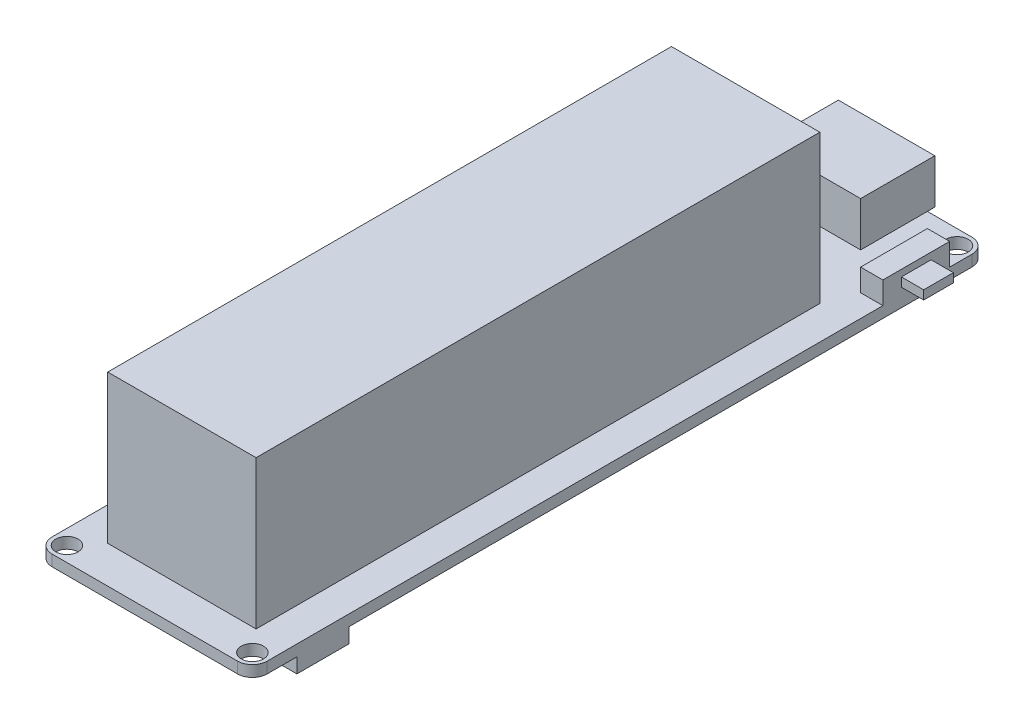
SolidWorks part; units mm, degrees
ref_plane "Front Plane" through (0, 0, 0) normal (0, 0, 1) x (1, 0, 0)
ref_plane "Top Plane" through (0, 0, 0) normal (0, 1, 0) x (1, 0, 0)
ref_plane "Right Plane" through (0, 0, 0) normal (1, 0, 0) x (0, 0, -1)
sketch "Sketch1" plane through (0, 0, 0) normal (0, 1, 0) x (1, 0, 0)
  line L1 (12.5, -49.5) -> (-12.5, -49.5)
  line L2 (14.5, -47.5) -> (14.5, 47.5)
  line L3 (12.5, 49.5) -> (-12.5, 49.5)
  line L4 (-14.5, -47.5) -> (-14.5, 47.5)
  line L5 (14.5, -49.5) -> (-14.5, 49.5) construction
  line L6 (14.5, 49.5) -> (-14.5, -49.5) construction
  arc A0 (14.5, 47.5) -> (12.5, 49.5) centre (12.5, 47.5) ccw
  arc A1 (14.5, -47.5) -> (12.5, -49.5) centre (12.5, -47.5) cw
  arc A2 (-12.5, -49.5) -> (-14.5, -47.5) centre (-12.5, -47.5) cw
  arc A3 (-14.5, 47.5) -> (-12.5, 49.5) centre (-12.5, 47.5) cw
  circle A4 centre (-12.5, 47.5) radius 1.5
  circle A5 centre (12.5, 47.5) radius 1.5
  circle A6 centre (-12.5, -47.5) radius 1.5
  circle A7 centre (12.5, -47.5) radius 1.5
  point P0 (0, 0)
  dimension "D3" = 2
  dimension "D4" = 2
  dimension "D5" = 2
  dimension "D6" = 2
  dimension "D7" = 3
  dimension "D8" = 3
  dimension "D9" = 3
  dimension "D10" = 3
  dimension "D1" = 29
  dimension "D2" = 99
extrude "Boss-Extrude1" add sketch "Sketch1" along normal blind 1.5
sketch "Sketch2" plane through (0, 1.5, 0) normal (0, 1, 0) x (1, 0, 0)
  line L0 (-12.5, -49.5) -> (12.5, -49.5) construction
  line L1 (-10, -44.5) -> (10, -44.5)
  line L2 (-10, -44.5) -> (-10, 31.5)
  line L3 (-10, 31.5) -> (10, 31.5)
  line L4 (10, -44.5) -> (10, 31.5)
  point P6 (0, -49.5)
  point P7 (0, -44.5)
  dimension "D1" = 20
  dimension "D2" = 76
  dimension "D3" = 5
extrude "Boss-Extrude2" add sketch "Sketch2" along normal blind 20
sketch "Sketch3" plane through (0, 1.5, 0) normal (0, 1, 0) x (1, 0, 0)
  line L0 (-14.5, 47.5) -> (-14.5, -47.5) construction
  line L1 (-6.5, 40.5) -> (6.5, 40.5)
  line L2 (-6.5, 40.5) -> (-6.5, 50.5)
  line L3 (-6.5, 50.5) -> (6.5, 50.5)
  line L4 (6.5, 40.5) -> (6.5, 50.5)
  line L5 (-14.5, 33.5) -> (-9.5, 33.5)
  line L6 (-14.5, 33.5) -> (-14.5, 40.5)
  line L7 (-14.5, 40.5) -> (-9.5, 40.5)
  line L8 (-9.5, 33.5) -> (-9.5, 40.5)
  line L9 (14.5, -47.5) -> (14.5, 47.5) construction
  line L10 (14.5, 44.5) -> (11.5, 44.5)
  line L11 (14.5, 44.5) -> (14.5, 35.5)
  line L12 (14.5, 35.5) -> (11.5, 35.5)
  line L13 (11.5, 44.5) -> (11.5, 35.5)
  line L14 (12.5, 49.5) -> (-12.5, 49.5) construction
  line L15 (10, 31.5) -> (-10, 31.5) construction
  point P20 (0, 49.5)
  point P21 (0, 40.5)
  line M15 (12.5, 49.5) -> (-12.5, 49.5)
  line M17 (-14.5, 47.5) -> (-14.5, -47.5)
  line M21 (14.5, -47.5) -> (14.5, 47.5)
  dimension "D1" = 9
  dimension "D2" = 7
  dimension "D3" = 5
  dimension "D4" = 3
  dimension "D5" = 13
  dimension "D6" = 10
  dimension "D7" = 1
  dimension "D8" = 5
  dimension "D9" = 2
extrude "Boss-Extrude3" add sketch "Sketch3" along normal blind 6 contours L1 L4 L2 M15 | L4 L3 L2 M15 region at (0, 1.5, -45) region at (0, 1.5, -50)
extrude "Boss-Extrude4" add sketch "Sketch3<3>" along normal blind 4 contours L5 L8 L7 M17 region at (-12, 1.5, -37)
sketch "Sketch3<3>" plane through (0, 1.5, 0) normal (0, 1, 0) x (1, 0, 0) same geometry as "Sketch3"
extrude "Boss-Extrude5" add sketch "Sketch3<4>" along normal blind 3 contours L10 L13 L12 M21 region at (13, 1.5, -40)
sketch "Sketch3<4>" plane through (0, 1.5, 0) normal (0, 1, 0) x (1, 0, 0) same geometry as "Sketch3"
sketch "Sketch4" plane through (-14.5, 0, 0) normal (-1, 0, 0) x (0, 0, 1)
  line L0 (-33.5, 5.5) -> (-40.5, 1.5) construction
  line L2 (-38.5, 4.5) -> (-35.5, 4.5)
  line L3 (-38.5, 4.5) -> (-38.5, 2.5)
  line L4 (-38.5, 2.5) -> (-35.5, 2.5)
  line L5 (-35.5, 4.5) -> (-35.5, 2.5)
  line L6 (-38.5, 4.5) -> (-35.5, 2.5) construction
  line L7 (-38.5, 2.5) -> (-35.5, 4.5) construction
  point P4 (-37, 3.5)
  dimension "D1" = 3
  dimension "D2" = 2
extrude "Boss-Extrude6" add sketch "Sketch4" along normal blind 1.2
sketch "Sketch5" plane through (14.5, 0, 0) normal (1, 0, 0) x (0, 0, -1)
  line L0 (35.5, 4.5) -> (44.5, 1.5) construction
  line L2 (38, 2.4) -> (42, 2.4)
  line L3 (38, 2.4) -> (38, 3.6)
  line L4 (38, 3.6) -> (42, 3.6)
  line L5 (42, 2.4) -> (42, 3.6)
  line L6 (38, 2.4) -> (42, 3.6) construction
  line L7 (38, 3.6) -> (42, 2.4) construction
  point P4 (40, 3)
  dimension "D1" = 1.2
  dimension "D2" = 4
extrude "Boss-Extrude7" add sketch "Sketch5" along normal blind 3
sketch "Sketch6" plane through (0, 0, 0) normal (0, -1, 0) x (1, 0, 0)
  line L0 (14.5, 47.5) -> (14.5, -47.5) construction
  line L1 (14.5, 43.5) -> (9.5, 43.5)
  line L2 (14.5, 43.5) -> (14.5, 36.5)
  line L3 (14.5, 36.5) -> (9.5, 36.5)
  line L4 (9.5, 43.5) -> (9.5, 36.5)
  line L6 (-15.5, 31) -> (-8.5, 31)
  line L7 (-15.5, 31) -> (-15.5, 22)
  line L8 (-15.5, 22) -> (-8.5, 22)
  line L9 (-8.5, 31) -> (-8.5, 22)
  line L10 (-12.5, 49.5) -> (12.5, 49.5) construction
  line L11 (-3, -1.5) -> (3.5, -1.5)
  line L12 (-3, -1.5) -> (-3, -8)
  line L13 (-3, -8) -> (3.5, -8)
  line L14 (3.5, -1.5) -> (3.5, -8)
  line L15 (-9.5, -29.6) -> (-8.4, -29.6)
  line L16 (-9.5, -29.6) -> (-9.5, -30.5)
  line L17 (-9.5, -30.5) -> (-8.4, -30.5)
  line L18 (-8.4, -29.6) -> (-8.4, -30.5)
  line L19 (-14.5, -47.5) -> (-14.5, 47.5) construction
  line L20 (12.5, -49.5) -> (-12.5, -49.5) construction
  line L21 (-9.5, -25.6) -> (-9.5, -26.5)
  line L22 (-9.5, -25.6) -> (-8.4, -25.6)
  line L23 (-8.4, -25.6) -> (-8.4, -26.5)
  line L24 (-9.5, -26.5) -> (-8.4, -26.5)
  line L25 (-9.5, -21.6) -> (-9.5, -22.5)
  line L26 (-9.5, -21.6) -> (-8.4, -21.6)
  line L27 (-8.4, -21.6) -> (-8.4, -22.5)
  line L28 (-9.5, -22.5) -> (-8.4, -22.5)
  line L29 (-9.5, -17.6) -> (-9.5, -18.5)
  line L30 (-9.5, -17.6) -> (-8.4, -17.6)
  line L31 (-8.4, -17.6) -> (-8.4, -18.5)
  line L32 (-9.5, -18.5) -> (-8.4, -18.5)
  line L33 (-9.5, -13.6) -> (-9.5, -14.5)
  line L34 (-9.5, -13.6) -> (-8.4, -13.6)
  line L35 (-8.4, -13.6) -> (-8.4, -14.5)
  line L36 (-9.5, -14.5) -> (-8.4, -14.5)
  line L37 (-9.5, -29.6) -> (-9.5, -25.6) construction
  line M11 (14.5, -47.5) -> (14.5, 47.5)
  line M15 (-14.5, 47.5) -> (-14.5, -47.5)
  dimension "D1" = 5
  dimension "D2" = 7
  dimension "D3" = 6
  dimension "D4" = 9
  dimension "D5" = 7
  dimension "D6" = 1
  dimension "D7" = 18.5
  dimension "D8" = 6.5
  dimension "D9" = 6.5
  dimension "D10" = 11
  dimension "D11" = 51
  dimension "D12" = 1.1
  dimension "D13" = 0.9
  dimension "D14" = 19
  dimension "D15" = 5
  dimension "D17" = 4
  dimension "D16" = 5
extrude "Boss-Extrude8" add sketch "Sketch6" along normal blind 0.2 contours L18 L15 L16 L17 | L21 L24 L23 L22 | L25 L28 L27 L26 | L29 L32 L31 L30 | L33 L36 L35 L34 region at (-8.95, 0, -30.05) region at (-8.95, 0, -26.05) region at (-8.95, 0, -22.05) region at (-8.95, 0, -18.05) region at (-8.95, 0, -14.05)
extrude "Boss-Extrude9" add sketch "Sketch6<3>" along normal blind 5 contours L14 L11 L12 L13 region at (0.25, 0, -4.75)
sketch "Sketch6<3>" plane through (0, 0, 0) normal (0, -1, 0) x (1, 0, 0) same geometry as "Sketch6"
extrude "Boss-Extrude10" add sketch "Sketch6<4>" along normal blind 3 contours L9 L6 L8 M15 region at (-11.5, 0, 26.5)
sketch "Sketch6<4>" plane through (0, 0, 0) normal (0, -1, 0) x (1, 0, 0) same geometry as "Sketch6"
extrude "Boss-Extrude11" add sketch "Sketch6<5>" along normal blind 2 contours L1 L4 L3 M11 region at (12, 0, 40)
sketch "Sketch6<5>" plane through (0, 0, 0) normal (0, -1, 0) x (1, 0, 0) same geometry as "Sketch6"
